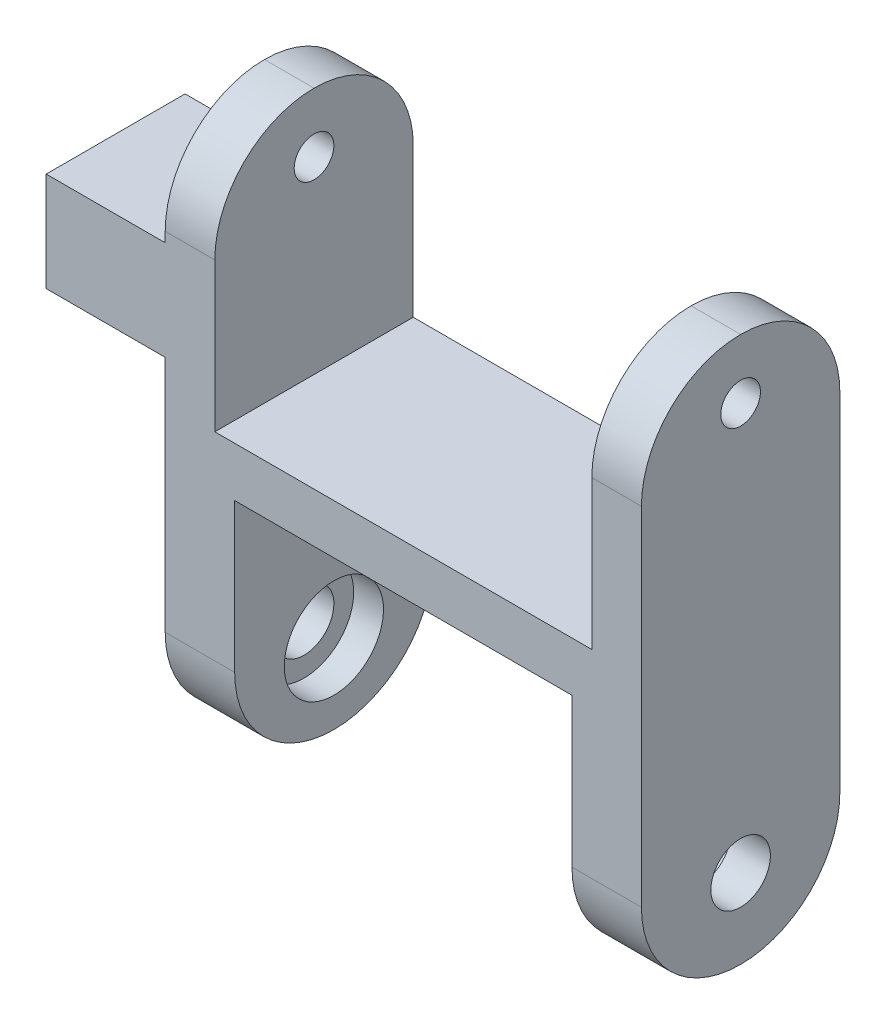
SolidWorks part; units mm, degrees
material "ABS"
ref_plane "Alzado" through (0, 0, 0) normal (0, 0, 1) x (1, 0, 0)
ref_plane "Planta" through (0, 0, 0) normal (0, 1, 0) x (1, 0, 0)
ref_plane "Vista lateral" through (0, 0, 0) normal (1, 0, 0) x (0, 0, -1)
sketch "Croquis1" plane through (0, 0, 0) normal (0, 0, 1) x (1, 0, 0)
  line L0 (8.5, 0) -> (-8.5, 0)
  line L1 (-8.5, 0) -> (-8.5, -12.5)
  line L2 (-8.5, -12.5) -> (-12, -12.5)
  line L3 (-12, -12.5) -> (-12, 2.5)
  line L4 (-9.5, 2.5) -> (9.5, 2.5)
  line L5 (0, 2.5) -> (0, 0) construction
  line L6 (12, -12.5) -> (12, 2.5)
  line L7 (8.5, -12.5) -> (12, -12.5)
  line L8 (8.5, 0) -> (8.5, -12.5)
  line L9 (-12, 2.5) -> (-12, 15)
  line L10 (-12, 15) -> (-9.5, 15)
  line L11 (-9.5, 15) -> (-9.5, 2.5)
  line L12 (9.5, 15) -> (9.5, 2.5)
  line L13 (12, 15) -> (9.5, 15)
  line L14 (12, 2.5) -> (12, 15)
  dimension "D1" = 8.5
  dimension "D2" = 12.5
  dimension "D3" = 3.5
  dimension "D4" = 2.5
  dimension "D5" = 12.5
  dimension "D6" = 9.5
extrude "Saliente-Extruir1" add sketch "Croquis1" along normal blind 10
sketch "Croquis2" plane through (-8.5, 0, 0) normal (1, 0, 0) x (0, 0, -1)
  line L0 (-10, -12.5) -> (0, -12.5) construction
  circle A0 centre (-5, -8.5) radius 2.5
  point P5 (-5, -12.5)
  dimension "D1" = 5
  dimension "D2" = 4
extrude "Cortar-Extruir1" cut sketch "Croquis2" against normal blind 1.5
sketch "Croquis3" plane through (-10, 0, 0) normal (1, 0, 0) x (0, 0, -1)
  circle A0 centre (-5, -8.5) radius 1.5
  dimension "D1" = 3
extrude "Cortar-Extruir2" cut sketch "Croquis3" against normal up to vertex (2 mm away) up to point (-12, -12.5, 10)
ref_plane "Plano1" through (0, 0, 0) normal (1, 0, 0) x (0, 0, -1)
mirror "Simetría1" about plane through (0, 0, 0) normal (1, 0, 0) of "Cortar-Extruir1", "Cortar-Extruir2"
sketch "Croquis6" plane through (-12, 0, 0) normal (-1, 0, 0) x (0, 0, 1)
  line L0 (10, 15) -> (0, 15) construction
  circle A0 centre (5, 12) radius 1
  dimension "D1" = 3
  dimension "D2" = 2
extrude "Cortar-Extruir3" cut sketch "Croquis6" against normal up to vertex (24 mm away) up to point (12, 15, 10)
sketch "Croquis9" plane through (-12, 0, 0) normal (-1, 0, 0) x (0, 0, 1)
  line L0 (10, 15) -> (10, -12.5) construction
  line L1 (3, 9.5) -> (10, 9.5)
  line L2 (3, 9.5) -> (3, 4.5)
  line L3 (3, 4.5) -> (10, 4.5)
  line L4 (10, 9.5) -> (10, 4.5)
  line L5 (5, -8.5) -> (5, 9.5) construction
  circle A0 centre (5, -8.5) radius 1.5 construction
  circle A1 centre (5, 7) radius 0.5
  point P13 (5, 6.9715)
  point P14 (3, 7)
  dimension "D4" = 1
  dimension "D1" = 13
  dimension "D2" = 5
  dimension "D3" = 7
extrude "Saliente-Extruir4" add sketch "Croquis9" along normal blind 6
sketch "Croquis10" plane through (0, 4.5, 0) normal (0, -1, 0) x (1, 0, 0)
  line L0 (-18, 10) -> (-12, 10) construction
  line L1 (-12, 3) -> (-15, 3)
  line L2 (-12, 3) -> (-12, 6)
  line L3 (-12, 6) -> (-15, 6)
  line L4 (-15, 3) -> (-15, 6)
  line L5 (-18, 3) -> (-18, 10) construction
  dimension "D1" = 4
  dimension "D2" = 3
extrude "Cortar-Extruir4" cut sketch "Croquis10" against normal up to vertex (5 mm away) up to point (-18, 9.5, 10)
fillet "Redondeo1" radius 5 8 edges at (10.25, -12.5, 10) (-10.25, -12.5, 10) (-10.25, -12.5, 0) (10.25, -12.5, 0) (-10.75, 15, 10) (-10.75, 15, 0) (10.75, 15, 10) (10.75, 15, 0)
